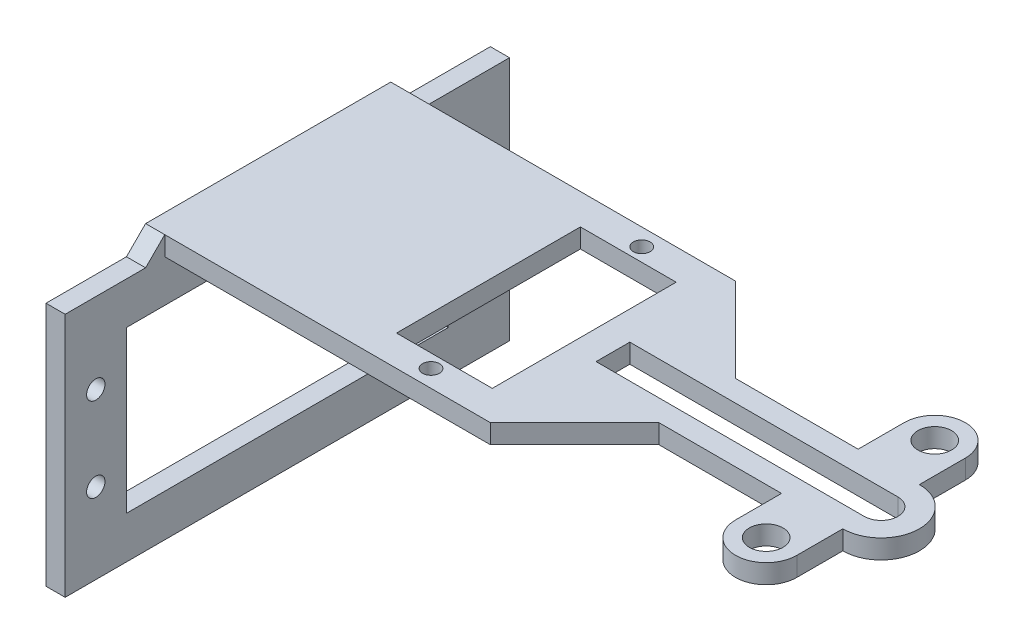
SolidWorks part; units mm, degrees
material "ABS"
ref_plane "Front Plane" through (0, 0, 0) normal (0, 0, 1) x (1, 0, 0)
ref_plane "Top Plane" through (0, 0, 0) normal (0, 1, 0) x (1, 0, 0)
ref_plane "Right Plane" through (0, 0, 0) normal (1, 0, 0) x (0, 0, -1)
sketch "Sketch1" plane through (0, 0, 0) normal (0, 1, 0) x (1, 0, 0)
  line L1 (-10, 16) -> (10, 16)
  line L2 (-10, 16) -> (-10, -16)
  line L3 (-10, -16) -> (10, -16)
  line L4 (10, 16) -> (10, -16)
  line L5 (-10, 16) -> (10, -16) construction
  line L6 (-10, -16) -> (10, 16) construction
  line L7 (-6.25, 12) -> (6.25, 12)
  line L8 (-6.25, 12) -> (-6.25, -12)
  line L9 (-6.25, -12) -> (6.25, -12)
  line L10 (6.25, 12) -> (6.25, -12)
  line L11 (-6.25, 12) -> (6.25, -12) construction
  line L12 (-6.25, -12) -> (6.25, 12) construction
  circle A0 centre (0, -13.75) radius 1.1
  circle A1 centre (0, 13.75) radius 1.1
  point P0 (0, 0)
  point P6 (0, 0)
  dimension "D7" = 2.2
  dimension "D1" = 20
  dimension "D2" = 32
  dimension "D3" = 24
  dimension "D4" = 12.5
  dimension "D5" = 13.75
  dimension "D6" = 13.75
extrude "Boss-Extrude1" add sketch "Sketch1" along normal blind 2.5
sketch "Sketch2" plane through (0, 2.5, 0) normal (0, 1, 0) x (1, 0, 0)
  line L0 (10, 0) -> (45, 0) construction
  line L1 (10, -16) -> (10, 16) construction
  line L2 (10, 5) -> (45, 5)
  line L3 (10, -5) -> (45, -5)
  line L4 (6.25, -12) -> (6.25, 12) construction
  line L5 (6.25, -3.3072) -> (6.25, 3.3072)
  line L6 (10, 0) -> (45, 0) construction
  line L7 (10, 2.2) -> (45, 2.2)
  line L8 (10, -2.2) -> (45, -2.2)
  arc A0 (10, 5) -> (6.25, 3.3072) centre (10, 0) ccw
  arc A1 (45, -5) -> (45, 5) centre (45, 0) ccw
  arc A2 (6.25, -3.3072) -> (10, -5) centre (10, 0) ccw
  arc A3 (10, 2.2) -> (10, -2.2) centre (10, 0) ccw
  arc A4 (45, -2.2) -> (45, 2.2) centre (45, 0) ccw
  point P5 (30, 0)
  point P14 (27.5, 0)
  dimension "D1" = 5
  dimension "D3" = 2.2
  dimension "D2" = 35
extrude "Boss-Extrude2" add sketch "Sketch2" against normal blind 2.5
chamfer "Chamfer1" distance 11 angle 45 2 edges at (10, 1.25, 5) (10, 1.25, -5)
sketch "Sketch3" plane through (0, 2.5, 0) normal (0, 1, 0) x (1, 0, 0)
  line L0 (-15.7036, 0) -> (62.831, 0) construction
  line L1 (45, -5) -> (45, -11)
  line L2 (37, -11) -> (37, -5)
  line L3 (21, -5) -> (45, -5) construction
  line L4 (37, -5) -> (45, -5)
  line L5 (45, 5) -> (45, 11)
  line L6 (37, 5) -> (45, 5)
  line L7 (37, 11) -> (37, 5)
  arc A0 (45, -11) -> (37, -11) centre (41, -11) cw
  circle A1 centre (41, -11) radius 2.2
  circle A2 centre (41, 11) radius 2.2
  arc A3 (45, 11) -> (37, 11) centre (41, 11) ccw
  dimension "D1" = 4
  dimension "D2" = 4.4
  dimension "D3" = 6
extrude "Boss-Extrude3" add sketch "Sketch3" against normal blind 2.5
sketch "Sketch4" plane through (0, 2.5, 0) normal (0, 1, 0) x (1, 0, 0)
  line L1 (-10, -16) -> (-35, -16)
  line L2 (-10, -16) -> (-10, 16)
  line L3 (-10, 16) -> (-35, 16)
  line L4 (-35, -16) -> (-35, 16)
  dimension "D1" = 32
  dimension "D2" = 25
extrude "Boss-Extrude4" add sketch "Sketch4" against normal blind 2.5
sketch "Sketch5" plane through (-35, 0, 0) normal (-1, 0, 0) x (0, 0, 1)
  line L1 (-29, 0) -> (29, 0)
  line L2 (-29, 0) -> (-29, -32)
  line L3 (-29, -32) -> (29, -32)
  line L4 (29, 0) -> (29, -32)
  line L5 (-21, -5.5) -> (21, -5.5)
  line L6 (-21, -5.5) -> (-21, -26.5)
  line L7 (-21, -26.5) -> (21, -26.5)
  line L8 (21, -5.5) -> (21, -26.5)
  line L9 (-21, -5.5) -> (21, -26.5) construction
  line L10 (-21, -26.5) -> (21, -5.5) construction
  circle A0 centre (25, -10.5) radius 1.2
  circle A1 centre (25, -21.5) radius 1.2
  circle A2 centre (-25, -10.5) radius 1.2
  circle A3 centre (-25, -21.5) radius 1.2
  point P4 (0, -16)
  dimension "D6" = 2.4
  dimension "D1" = 58
  dimension "D2" = 32
  dimension "D3" = 42
  dimension "D4" = 21
  dimension "D5" = 5.5
  dimension "D7" = 5
  dimension "D8" = 4
  dimension "D9" = 4
  dimension "D10" = 5
extrude "Boss-Extrude5" add sketch "Sketch5" against normal blind 2.5
chamfer "Chamfer2" distance 2.5 angle 45 2 edges at (-33.75, 0, -16) (-33.75, 0, 16)
